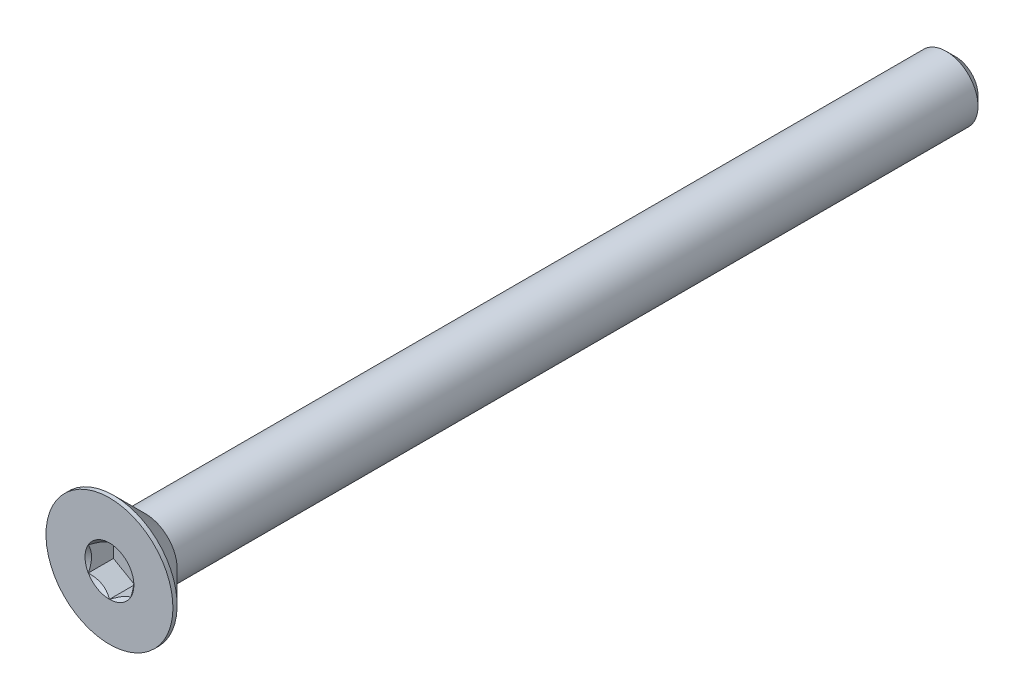
SolidWorks part; units mm, degrees
material "Alloy Steel"
ref_plane "Front" through (0, 0, 0) normal (0, 0, 1) x (1, 0, 0)
ref_plane "Top" through (0, 0, 0) normal (0, 1, 0) x (1, 0, 0)
ref_plane "Right" through (0, 0, 0) normal (1, 0, 0) x (0, 0, -1)
sketch "Sketch1" plane through (0, 0, 0) normal (1, 0, 0) x (0, 0, -1)
  line L0 (-20, 3) -> (-19.8, 3) construction
  line L1 (-19.8, 3) -> (-18.3, 1.5) construction
  line L2 (-20, 1.5) -> (20, 1.5) construction
  line L3 (20, 1.5) -> (20, 0) construction
  line L4 (20, 0) -> (-20, 0) construction
  line L5 (-20, 0) -> (-20, 3) construction
  line L6 (-20, 3) -> (-20, -3) construction
  line L7 (20, 1.5) -> (20, -1.5) construction
  line L8 (-20, -3) -> (-19.8, -3) construction
  line L9 (-19.8, -3) -> (-18.3, -1.5) construction
  line L11 (-20, 1.5) -> (-20, 0) construction
  line L12 (-18.3, 1.5) -> (-18.3, 0) construction
  line L13 (19.9688, 1.5541) -> (20.2188, 1.1211) construction
  line L14 (20.2188, 1.1211) -> (20.4688, 1.5541) construction
  line L15 (20.4688, 1.5541) -> (19.9688, 1.5541) construction
  line L16 (20.2188, 1.5541) -> (20.2188, 1.5) construction
  line L17 (20.2188, 1.5) -> (20.2188, 1.1752) construction
  line L18 (20.2188, 1.1752) -> (20.2188, 1.1211) construction
  line L19 (20.2188, 1.5271) -> (20.4531, 1.5271) construction
  line L20 (20.2188, 1.5271) -> (19.9844, 1.5271) construction
  line L21 (20, 1.5) -> (20.4375, 1.5) construction
  line L22 (20.1875, 1.1752) -> (20.25, 1.1752) construction
  line L23 (20, -1.5) -> (-18.3, -1.5) construction
  point P10 (18.75, -1.5)
  point P24 (-8.3, 1.5)
  point P30 (0, 0)
  dimension "Head Diameter" = 6
  dimension "Head Height" = 1.7
  dimension "Length" = 40
  dimension "Countersink Angle" = 90
  dimension "Thread Pitch" = 0.5
  dimension "D2" = 0.0625
  dimension "Minimum Thread Length" = 28.3
  dimension "Thread Size" = 3
  dimension "D1" = 1.25
sketch "Sketch2" plane through (0, 0, 0) normal (0, 0, 1) x (1, 0, 0)
  line L1 (0, 1.1547) -> (-1, 0.5774) construction
  line L2 (-1, 0.5774) -> (-1, -0.5774) construction
  line L3 (-1, -0.5774) -> (0, -1.1547) construction
  line L4 (0, -1.1547) -> (1, -0.5774) construction
  line L5 (1, -0.5774) -> (1, 0.5774) construction
  line L6 (1, 0.5774) -> (0, 1.1547) construction
  circle A0 centre (0, 0) radius 1 construction
  dimension "Drive Size" = 2
sketch "Sketch3" plane through (0, 0, 0) normal (1, 0, 0) x (0, 0, -1)
  line L0 (-20, 1.5) -> (20, 1.5)
  line L1 (20, 1.5) -> (20, 0)
  line L2 (20, 0) -> (-20, 0)
  line L3 (-20, 0) -> (-20, 1.5)
revolve "Revolve1" add sketch "Sketch3" angle 360 about L4
chamfer "Chamfer1" distance 0.45 angle 45 1 edges at (0, 1.5, -20)
sketch "Sketch6" plane through (0, 0, 0) normal (1, 0, 0) x (0, 0, -1)
  line L0 (-20, 3) -> (-19.8, 3)
  line L1 (-19.8, 3) -> (-18.3, 1.5)
  line L2 (-18.3, 1.5) -> (-18.3, 0)
  line L3 (-18.3, 0) -> (-20, 0)
  line L4 (-20, 0) -> (-20, 3)
revolve "Revolve2" add sketch "Sketch6" angle 360 about L4
sketch "Sketch8" plane through (0, 0, 20) normal (0, 0, 1) x (1, 0, 0)
  line L0 (0, 1.1547) -> (-1, 0.5774) construction
  line L1 (1, 0.5774) -> (0, 1.1547) construction
  line L2 (1, -0.5774) -> (1, 0.5774) construction
  line L3 (0, -1.1547) -> (1, -0.5774) construction
  line L4 (-1, 0.5774) -> (-1, -0.5774) construction
  line L5 (-1, -0.5774) -> (0, -1.1547) construction
  line L6 (0, 1.1547) -> (-1, 0.5774)
  line L7 (1, 0.5774) -> (0, 1.1547)
  line L8 (1, -0.5774) -> (1, 0.5774)
  line L9 (0, -1.1547) -> (1, -0.5774)
  line L10 (-1, 0.5774) -> (-1, -0.5774)
  line L11 (-1, -0.5774) -> (0, -1.1547)
extrude "Cut-Extrude1" cut sketch "Sketch8" against normal blind 1.19
sketch "Sketch9" plane through (0, 0, 20) normal (0, 0, 1) x (1, 0, 0)
  circle A0 centre (0, 0) radius 1.1547
extrude "Cut-Extrude2" cut sketch "Sketch9" against normal up to next (1.19 mm away) draft 45
ref_plane "Plane1" [suppressed] through (0, 0, 13.3) normal (0, 0, 1) x (1, 0, 0)
split "Split1" [suppressed] bodies to split 124
sketch "Sketch4" [suppressed] plane through (0, 0, -15) normal (0, 0, -1) x (-1, 0, 0)
  circle A0 centre (0, 0) radius 1.5 construction
  circle A1 centre (0, 0) radius 1.5
curve "Helix/Spiral1" [suppressed] pitch 0.5 height 28.8 turns 57.6
sketch "Sketch10" [suppressed] plane through (0, 0, 0) normal (1, 0, 0) x (0, 0, -1)
  line L0 (14.9844, 1.5271) -> (15.4531, 1.5271)
  line L1 (15.4531, 1.5271) -> (15.25, 1.1752)
  line L2 (15.25, 1.1752) -> (15.1875, 1.1752)
  line L3 (15.1875, 1.1752) -> (14.9844, 1.5271)
sweep "Cut-Sweep1" [suppressed] cut profiles "Sketch10" path "Helix/Spiral1"
equation "\"D2@Sketch1\" = \"Thread Pitch@Sketch1\" / 8"
equation "\"D4@Helix/Spiral1\"=\"Thread Pitch@Sketch1\""
equation "\"D3@Helix/Spiral1\"=\"Minimum Thread Length@Sketch1\"+\"Thread Pitch@Sketch1\""
equation "\"D1@Chamfer1\"=\"Thread Size@Sketch1\"*.15"
equation "\"D1@Cut-Extrude1\"=\"Head Height@Sketch1\"*.7"
equation "\"D1@Sketch1\"=\"Thread Pitch@Sketch1\"*2.5"
